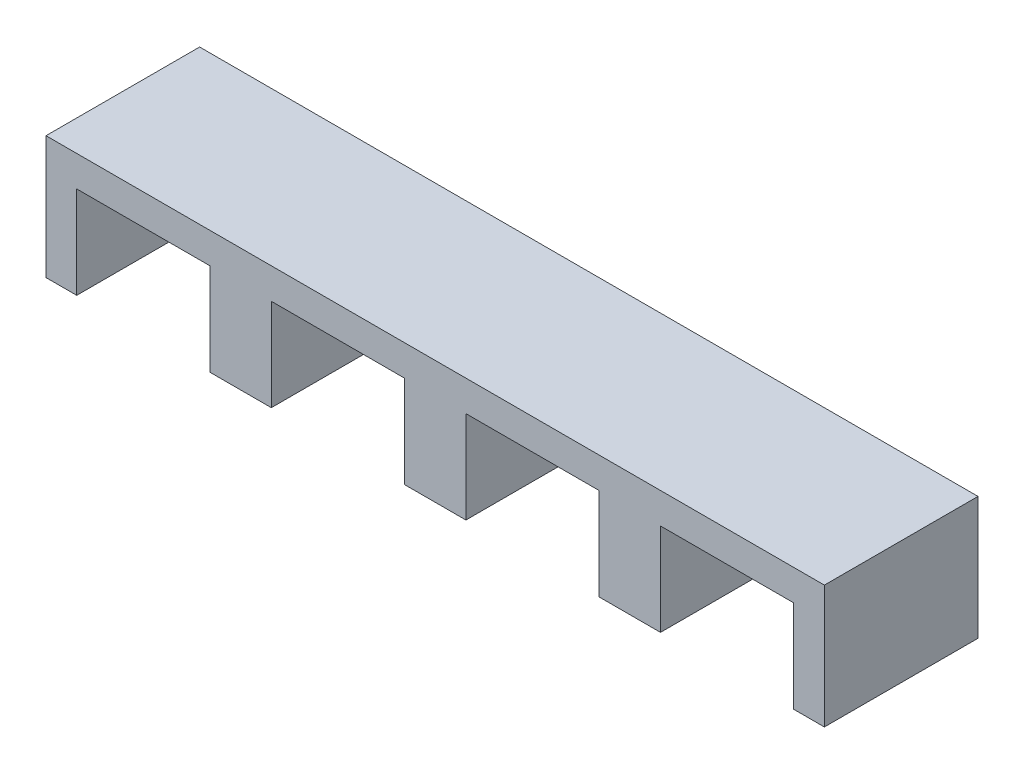
SolidWorks part; units mm, degrees
ref_plane "Front Plane" through (0, 0, 0) normal (0, 0, 1) x (1, 0, 0)
ref_plane "Top Plane" through (0, 0, 0) normal (0, 1, 0) x (1, 0, 0)
ref_plane "Right Plane" through (0, 0, 0) normal (1, 0, 0) x (0, 0, -1)
sketch "Esquisse1" plane through (0, 0, 0) normal (0, 0, 1) x (1, 0, 0)
  line L0 (3, 0) -> (3, 9)
  line L1 (3, 9) -> (16, 9)
  line L2 (16, 9) -> (16, 0)
  line L3 (16, 0) -> (22, 0)
  line L4 (22, 0) -> (22, 9)
  line L5 (22, 9) -> (35, 9)
  line L6 (35, 9) -> (35, 0)
  line L7 (35, 0) -> (41, 0)
  line L8 (41, 0) -> (41, 9)
  line L9 (41, 9) -> (54, 9)
  line L10 (54, 9) -> (54, 0)
  line L11 (54, 0) -> (60, 0)
  line L12 (76, 0) -> (76, 12)
  line L13 (76, 12) -> (0, 12)
  line L14 (0, 12) -> (0, 0)
  line L15 (0, 0) -> (3, 0)
  line L16 (60, 0) -> (60, 9)
  line L17 (60, 9) -> (73, 9)
  line L18 (73, 9) -> (73, 0)
  line L19 (73, 0) -> (76, 0)
  point P20 (-13.8525, 7.1943)
  point P22 (48.9806, 6.9368)
  point P23 (25.1607, 7)
  point P24 (0, 0)
  dimension "D1" = 13
  dimension "D2" = 6
  dimension "D3" = 6
  dimension "D4" = 6
  dimension "D5" = 3
  dimension "D6" = 3
  dimension "D7" = 12
  dimension "D8" = 3
extrude "Main" add sketch "Esquisse1" along normal blind 15
